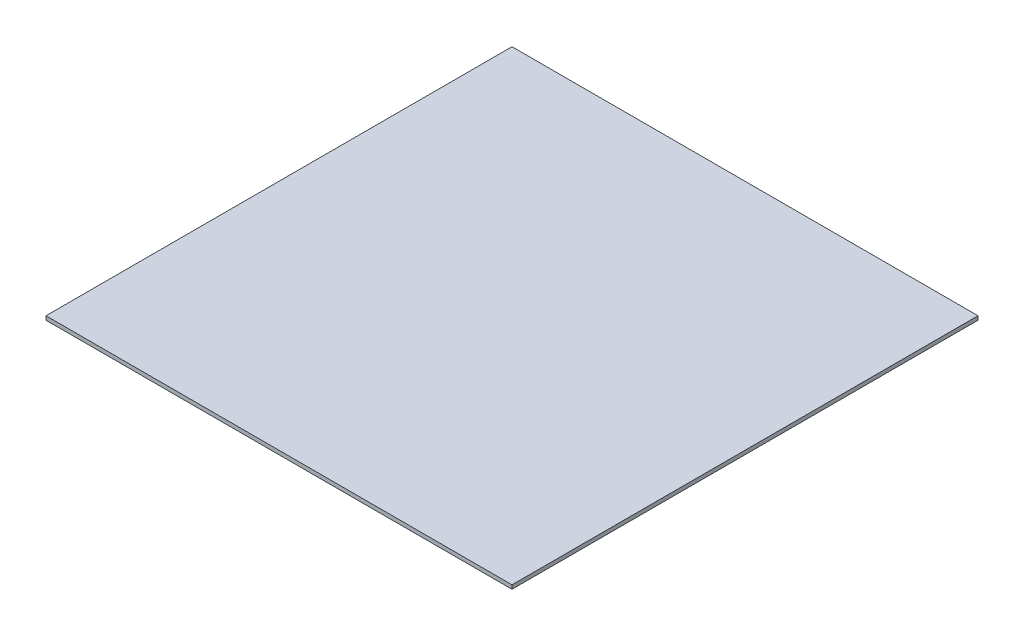
SolidWorks part; units mm, degrees
ref_plane "Front Plane" through (0, 0, 0) normal (0, 0, 1) x (1, 0, 0)
ref_plane "Top Plane" through (0, 0, 0) normal (0, 1, 0) x (1, 0, 0)
ref_plane "Right Plane" through (0, 0, 0) normal (1, 0, 0) x (0, 0, -1)
sketch "Sketch1" plane through (-19.0745, -1092.5733, -406.9173) normal (0, -1, 0) x (1, 0, 0)
  line L5 (-240, -240) -> (240, -240) construction
  line L6 (-240, -240) -> (-240, 240) construction
  line L7 (-240, 240) -> (240, 240) construction
  line L8 (240, -240) -> (240, 240) construction
  line L9 (-240, -240) -> (240, 240) construction
  line L10 (-240, 240) -> (240, -240) construction
  line L11 (300, -300) -> (-300, -300)
  line L12 (300, -300) -> (300, 300)
  line L13 (300, 300) -> (-300, 300)
  line L14 (-300, -300) -> (-300, 300)
  line L15 (300, -300) -> (-300, 300) construction
  line L16 (300, 300) -> (-300, -300) construction
  point P0 (0, 0)
  point P5 (0, 0)
  point P7 (-240, -240)
  dimension "D1" = 480
  dimension "D2" = 480
  dimension "D3" = 600
  dimension "D4" = 600
extrude "Boss-Extrude1" add sketch "Sketch1" along normal blind 5 contours L13 L14 L11 L12
sketch "Sketch3" plane through (0, -1092.5733, 0) normal (0, 1, 0) x (1, 0, 0)
  line L0 (-199.0745, 166.9173) -> (-199.0745, 226.9173)
  line L1 (-259.0745, 166.9173) -> (-199.0745, 166.9173)
  line L2 (-259.0745, 166.9173) -> (-259.0745, 226.9173)
  line L3 (-259.0745, 226.9173) -> (-199.0745, 226.9173)
  line L4 (-199.0745, 166.9173) -> (-199.0745, 226.9173)
  line L5 (-199.0745, 166.9173) -> (-139.0745, 166.9173)
  line L6 (-139.0745, 166.9173) -> (-139.0745, 226.9173)
  line L7 (-199.0745, 226.9173) -> (-139.0745, 226.9173)
  line L8 (-139.0745, 166.9173) -> (-139.0745, 226.9173)
  line L9 (-139.0745, 166.9173) -> (-79.0745, 166.9173)
  line L10 (-79.0745, 166.9173) -> (-79.0745, 226.9173)
  line L11 (-139.0745, 226.9173) -> (-79.0745, 226.9173)
  line L12 (-79.0745, 166.9173) -> (-79.0745, 226.9173)
  line L13 (-79.0745, 166.9173) -> (-19.0745, 166.9173)
  line L14 (-19.0745, 166.9173) -> (-19.0745, 226.9173)
  line L15 (-79.0745, 226.9173) -> (-19.0745, 226.9173)
  line L16 (-19.0745, 166.9173) -> (-19.0745, 226.9173)
  line L17 (-19.0745, 166.9173) -> (40.9255, 166.9173)
  line L18 (40.9255, 166.9173) -> (40.9255, 226.9173)
  line L19 (-19.0745, 226.9173) -> (40.9255, 226.9173)
  line L20 (40.9255, 166.9173) -> (40.9255, 226.9173)
  line L21 (40.9255, 166.9173) -> (100.9255, 166.9173)
  line L22 (100.9255, 166.9173) -> (100.9255, 226.9173)
  line L23 (40.9255, 226.9173) -> (100.9255, 226.9173)
  line L24 (100.9255, 166.9173) -> (100.9255, 226.9173)
  line L25 (100.9255, 166.9173) -> (160.9255, 166.9173)
  line L26 (160.9255, 166.9173) -> (160.9255, 226.9173)
  line L27 (100.9255, 226.9173) -> (160.9255, 226.9173)
  line L28 (160.9255, 166.9173) -> (160.9255, 226.9173)
  line L29 (160.9255, 166.9173) -> (220.9255, 166.9173)
  line L30 (220.9255, 166.9173) -> (220.9255, 226.9173)
  line L31 (160.9255, 226.9173) -> (220.9255, 226.9173)
  line L32 (-199.0745, 226.9173) -> (-199.0745, 286.9173)
  line L33 (-199.0745, 226.9173) -> (-139.0745, 226.9173)
  line L34 (-139.0745, 226.9173) -> (-139.0745, 286.9173)
  line L35 (-199.0745, 286.9173) -> (-139.0745, 286.9173)
  line L36 (-139.0745, 226.9173) -> (-139.0745, 286.9173)
  line L37 (-139.0745, 226.9173) -> (-79.0745, 226.9173)
  line L38 (-79.0745, 226.9173) -> (-79.0745, 286.9173)
  line L39 (-139.0745, 286.9173) -> (-79.0745, 286.9173)
  line L40 (-79.0745, 226.9173) -> (-79.0745, 286.9173)
  line L41 (-79.0745, 226.9173) -> (-19.0745, 226.9173)
  line L42 (-19.0745, 226.9173) -> (-19.0745, 286.9173)
  line L43 (-79.0745, 286.9173) -> (-19.0745, 286.9173)
  line L44 (-19.0745, 226.9173) -> (-19.0745, 286.9173)
  line L45 (-19.0745, 226.9173) -> (40.9255, 226.9173)
  line L46 (40.9255, 226.9173) -> (40.9255, 286.9173)
  line L47 (-19.0745, 286.9173) -> (40.9255, 286.9173)
  line L48 (40.9255, 226.9173) -> (40.9255, 286.9173)
  line L49 (40.9255, 226.9173) -> (100.9255, 226.9173)
  line L50 (100.9255, 226.9173) -> (100.9255, 286.9173)
  line L51 (40.9255, 286.9173) -> (100.9255, 286.9173)
  line L52 (100.9255, 226.9173) -> (100.9255, 286.9173)
  line L53 (100.9255, 226.9173) -> (160.9255, 226.9173)
  line L54 (160.9255, 226.9173) -> (160.9255, 286.9173)
  line L55 (100.9255, 286.9173) -> (160.9255, 286.9173)
  line L56 (160.9255, 226.9173) -> (160.9255, 286.9173)
  line L57 (160.9255, 226.9173) -> (220.9255, 226.9173)
  line L58 (220.9255, 226.9173) -> (220.9255, 286.9173)
  line L59 (160.9255, 286.9173) -> (220.9255, 286.9173)
  line L60 (-199.0745, 286.9173) -> (-199.0745, 346.9173)
  line L61 (-199.0745, 286.9173) -> (-139.0745, 286.9173)
  line L62 (-139.0745, 286.9173) -> (-139.0745, 346.9173)
  line L63 (-199.0745, 346.9173) -> (-139.0745, 346.9173)
  line L64 (-139.0745, 286.9173) -> (-139.0745, 346.9173)
  line L65 (-139.0745, 286.9173) -> (-79.0745, 286.9173)
  line L66 (-79.0745, 286.9173) -> (-79.0745, 346.9173)
  line L67 (-139.0745, 346.9173) -> (-79.0745, 346.9173)
  line L68 (-79.0745, 286.9173) -> (-79.0745, 346.9173)
  line L69 (-79.0745, 286.9173) -> (-19.0745, 286.9173)
  line L70 (-19.0745, 286.9173) -> (-19.0745, 346.9173)
  line L71 (-79.0745, 346.9173) -> (-19.0745, 346.9173)
  line L72 (-19.0745, 286.9173) -> (-19.0745, 346.9173)
  line L73 (-19.0745, 286.9173) -> (40.9255, 286.9173)
  line L74 (40.9255, 286.9173) -> (40.9255, 346.9173)
  line L75 (-19.0745, 346.9173) -> (40.9255, 346.9173)
  line L76 (40.9255, 286.9173) -> (40.9255, 346.9173)
  line L77 (40.9255, 286.9173) -> (100.9255, 286.9173)
  line L78 (100.9255, 286.9173) -> (100.9255, 346.9173)
  line L79 (40.9255, 346.9173) -> (100.9255, 346.9173)
  line L80 (100.9255, 286.9173) -> (100.9255, 346.9173)
  line L81 (100.9255, 286.9173) -> (160.9255, 286.9173)
  line L82 (160.9255, 286.9173) -> (160.9255, 346.9173)
  line L83 (100.9255, 346.9173) -> (160.9255, 346.9173)
  line L84 (160.9255, 286.9173) -> (160.9255, 346.9173)
  line L85 (160.9255, 286.9173) -> (220.9255, 286.9173)
  line L86 (220.9255, 286.9173) -> (220.9255, 346.9173)
  line L87 (160.9255, 346.9173) -> (220.9255, 346.9173)
  line L88 (-199.0745, 346.9173) -> (-199.0745, 406.9173)
  line L89 (-199.0745, 346.9173) -> (-139.0745, 346.9173)
  line L90 (-139.0745, 346.9173) -> (-139.0745, 406.9173)
  line L91 (-199.0745, 406.9173) -> (-139.0745, 406.9173)
  line L92 (-139.0745, 346.9173) -> (-139.0745, 406.9173)
  line L93 (-139.0745, 346.9173) -> (-79.0745, 346.9173)
  line L94 (-79.0745, 346.9173) -> (-79.0745, 406.9173)
  line L95 (-139.0745, 406.9173) -> (-79.0745, 406.9173)
  line L96 (-79.0745, 346.9173) -> (-79.0745, 406.9173)
  line L97 (-79.0745, 346.9173) -> (-19.0745, 346.9173)
  line L98 (-19.0745, 346.9173) -> (-19.0745, 406.9173)
  line L99 (-79.0745, 406.9173) -> (-19.0745, 406.9173)
  line L100 (-19.0745, 346.9173) -> (-19.0745, 406.9173)
  line L101 (-19.0745, 346.9173) -> (40.9255, 346.9173)
  line L102 (40.9255, 346.9173) -> (40.9255, 406.9173)
  line L103 (-19.0745, 406.9173) -> (40.9255, 406.9173)
  line L104 (40.9255, 346.9173) -> (40.9255, 406.9173)
  line L105 (40.9255, 346.9173) -> (100.9255, 346.9173)
  line L106 (100.9255, 346.9173) -> (100.9255, 406.9173)
  line L107 (40.9255, 406.9173) -> (100.9255, 406.9173)
  line L108 (100.9255, 346.9173) -> (100.9255, 406.9173)
  line L109 (100.9255, 346.9173) -> (160.9255, 346.9173)
  line L110 (160.9255, 346.9173) -> (160.9255, 406.9173)
  line L111 (100.9255, 406.9173) -> (160.9255, 406.9173)
  line L112 (160.9255, 346.9173) -> (160.9255, 406.9173)
  line L113 (160.9255, 346.9173) -> (220.9255, 346.9173)
  line L114 (220.9255, 346.9173) -> (220.9255, 406.9173)
  line L115 (160.9255, 406.9173) -> (220.9255, 406.9173)
  line L116 (-199.0745, 406.9173) -> (-199.0745, 466.9173)
  line L117 (-199.0745, 406.9173) -> (-139.0745, 406.9173)
  line L118 (-139.0745, 406.9173) -> (-139.0745, 466.9173)
  line L119 (-199.0745, 466.9173) -> (-139.0745, 466.9173)
  line L120 (-139.0745, 406.9173) -> (-139.0745, 466.9173)
  line L121 (-139.0745, 406.9173) -> (-79.0745, 406.9173)
  line L122 (-79.0745, 406.9173) -> (-79.0745, 466.9173)
  line L123 (-139.0745, 466.9173) -> (-79.0745, 466.9173)
  line L124 (-79.0745, 406.9173) -> (-79.0745, 466.9173)
  line L125 (-79.0745, 406.9173) -> (-19.0745, 406.9173)
  line L126 (-19.0745, 406.9173) -> (-19.0745, 466.9173)
  line L127 (-79.0745, 466.9173) -> (-19.0745, 466.9173)
  line L128 (-19.0745, 406.9173) -> (-19.0745, 466.9173)
  line L129 (-19.0745, 406.9173) -> (40.9255, 406.9173)
  line L130 (40.9255, 406.9173) -> (40.9255, 466.9173)
  line L131 (-19.0745, 466.9173) -> (40.9255, 466.9173)
  line L132 (40.9255, 406.9173) -> (40.9255, 466.9173)
  line L133 (40.9255, 406.9173) -> (100.9255, 406.9173)
  line L134 (100.9255, 406.9173) -> (100.9255, 466.9173)
  line L135 (40.9255, 466.9173) -> (100.9255, 466.9173)
  line L136 (100.9255, 406.9173) -> (100.9255, 466.9173)
  line L137 (100.9255, 406.9173) -> (160.9255, 406.9173)
  line L138 (160.9255, 406.9173) -> (160.9255, 466.9173)
  line L139 (100.9255, 466.9173) -> (160.9255, 466.9173)
  line L140 (160.9255, 406.9173) -> (160.9255, 466.9173)
  line L141 (160.9255, 406.9173) -> (220.9255, 406.9173)
  line L142 (220.9255, 406.9173) -> (220.9255, 466.9173)
  line L143 (160.9255, 466.9173) -> (220.9255, 466.9173)
  line L144 (-199.0745, 466.9173) -> (-199.0745, 526.9173)
  line L145 (-199.0745, 466.9173) -> (-139.0745, 466.9173)
  line L146 (-139.0745, 466.9173) -> (-139.0745, 526.9173)
  line L147 (-199.0745, 526.9173) -> (-139.0745, 526.9173)
  line L148 (-139.0745, 466.9173) -> (-139.0745, 526.9173)
  line L149 (-139.0745, 466.9173) -> (-79.0745, 466.9173)
  line L150 (-79.0745, 466.9173) -> (-79.0745, 526.9173)
  line L151 (-139.0745, 526.9173) -> (-79.0745, 526.9173)
  line L152 (-79.0745, 466.9173) -> (-79.0745, 526.9173)
  line L153 (-79.0745, 466.9173) -> (-19.0745, 466.9173)
  line L154 (-19.0745, 466.9173) -> (-19.0745, 526.9173)
  line L155 (-79.0745, 526.9173) -> (-19.0745, 526.9173)
  line L156 (-19.0745, 466.9173) -> (-19.0745, 526.9173)
  line L157 (-19.0745, 466.9173) -> (40.9255, 466.9173)
  line L158 (40.9255, 466.9173) -> (40.9255, 526.9173)
  line L159 (-19.0745, 526.9173) -> (40.9255, 526.9173)
  line L160 (40.9255, 466.9173) -> (40.9255, 526.9173)
  line L161 (40.9255, 466.9173) -> (100.9255, 466.9173)
  line L162 (100.9255, 466.9173) -> (100.9255, 526.9173)
  line L163 (40.9255, 526.9173) -> (100.9255, 526.9173)
  line L164 (100.9255, 466.9173) -> (100.9255, 526.9173)
  line L165 (100.9255, 466.9173) -> (160.9255, 466.9173)
  line L166 (160.9255, 466.9173) -> (160.9255, 526.9173)
  line L167 (100.9255, 526.9173) -> (160.9255, 526.9173)
  line L168 (160.9255, 466.9173) -> (160.9255, 526.9173)
  line L169 (160.9255, 466.9173) -> (220.9255, 466.9173)
  line L170 (220.9255, 466.9173) -> (220.9255, 526.9173)
  line L171 (160.9255, 526.9173) -> (220.9255, 526.9173)
  line L172 (-199.0745, 526.9173) -> (-199.0745, 586.9173)
  line L173 (-199.0745, 526.9173) -> (-139.0745, 526.9173)
  line L174 (-139.0745, 526.9173) -> (-139.0745, 586.9173)
  line L175 (-199.0745, 586.9173) -> (-139.0745, 586.9173)
  line L176 (-139.0745, 526.9173) -> (-139.0745, 586.9173)
  line L177 (-139.0745, 526.9173) -> (-79.0745, 526.9173)
  line L178 (-79.0745, 526.9173) -> (-79.0745, 586.9173)
  line L179 (-139.0745, 586.9173) -> (-79.0745, 586.9173)
  line L180 (-79.0745, 526.9173) -> (-79.0745, 586.9173)
  line L181 (-79.0745, 526.9173) -> (-19.0745, 526.9173)
  line L182 (-19.0745, 526.9173) -> (-19.0745, 586.9173)
  line L183 (-79.0745, 586.9173) -> (-19.0745, 586.9173)
  line L184 (-19.0745, 526.9173) -> (-19.0745, 586.9173)
  line L185 (-19.0745, 526.9173) -> (40.9255, 526.9173)
  line L186 (40.9255, 526.9173) -> (40.9255, 586.9173)
  line L187 (-19.0745, 586.9173) -> (40.9255, 586.9173)
  line L188 (40.9255, 526.9173) -> (40.9255, 586.9173)
  line L189 (40.9255, 526.9173) -> (100.9255, 526.9173)
  line L190 (100.9255, 526.9173) -> (100.9255, 586.9173)
  line L191 (40.9255, 586.9173) -> (100.9255, 586.9173)
  line L192 (100.9255, 526.9173) -> (100.9255, 586.9173)
  line L193 (100.9255, 526.9173) -> (160.9255, 526.9173)
  line L194 (160.9255, 526.9173) -> (160.9255, 586.9173)
  line L195 (100.9255, 586.9173) -> (160.9255, 586.9173)
  line L196 (160.9255, 526.9173) -> (160.9255, 586.9173)
  line L197 (160.9255, 526.9173) -> (220.9255, 526.9173)
  line L198 (220.9255, 526.9173) -> (220.9255, 586.9173)
  line L199 (160.9255, 586.9173) -> (220.9255, 586.9173)
  line L200 (-199.0745, 586.9173) -> (-199.0745, 646.9173)
  line L201 (-199.0745, 586.9173) -> (-139.0745, 586.9173)
  line L202 (-139.0745, 586.9173) -> (-139.0745, 646.9173)
  line L203 (-199.0745, 646.9173) -> (-139.0745, 646.9173)
  line L204 (-139.0745, 586.9173) -> (-139.0745, 646.9173)
  line L205 (-139.0745, 586.9173) -> (-79.0745, 586.9173)
  line L206 (-79.0745, 586.9173) -> (-79.0745, 646.9173)
  line L207 (-139.0745, 646.9173) -> (-79.0745, 646.9173)
  line L208 (-79.0745, 586.9173) -> (-79.0745, 646.9173)
  line L209 (-79.0745, 586.9173) -> (-19.0745, 586.9173)
  line L210 (-19.0745, 586.9173) -> (-19.0745, 646.9173)
  line L211 (-79.0745, 646.9173) -> (-19.0745, 646.9173)
  line L212 (-19.0745, 586.9173) -> (-19.0745, 646.9173)
  line L213 (-19.0745, 586.9173) -> (40.9255, 586.9173)
  line L214 (40.9255, 586.9173) -> (40.9255, 646.9173)
  line L215 (-19.0745, 646.9173) -> (40.9255, 646.9173)
  line L216 (40.9255, 586.9173) -> (40.9255, 646.9173)
  line L217 (40.9255, 586.9173) -> (100.9255, 586.9173)
  line L218 (100.9255, 586.9173) -> (100.9255, 646.9173)
  line L219 (40.9255, 646.9173) -> (100.9255, 646.9173)
  line L220 (100.9255, 586.9173) -> (100.9255, 646.9173)
  line L221 (100.9255, 586.9173) -> (160.9255, 586.9173)
  line L222 (160.9255, 586.9173) -> (160.9255, 646.9173)
  line L223 (100.9255, 646.9173) -> (160.9255, 646.9173)
  line L224 (160.9255, 586.9173) -> (160.9255, 646.9173)
  line L225 (160.9255, 586.9173) -> (220.9255, 586.9173)
  line L226 (220.9255, 586.9173) -> (220.9255, 646.9173)
  line L227 (160.9255, 646.9173) -> (220.9255, 646.9173)
  line L228 (-259.0745, 226.9173) -> (-259.0745, 286.9173)
  line L229 (-259.0745, 226.9173) -> (-199.0745, 226.9173)
  line L230 (-199.0745, 226.9173) -> (-199.0745, 286.9173)
  line L231 (-259.0745, 286.9173) -> (-199.0745, 286.9173)
  line L232 (-259.0745, 286.9173) -> (-259.0745, 346.9173)
  line L233 (-259.0745, 286.9173) -> (-199.0745, 286.9173)
  line L234 (-199.0745, 286.9173) -> (-199.0745, 346.9173)
  line L235 (-259.0745, 346.9173) -> (-199.0745, 346.9173)
  line L236 (-259.0745, 346.9173) -> (-259.0745, 406.9173)
  line L237 (-259.0745, 346.9173) -> (-199.0745, 346.9173)
  line L238 (-199.0745, 346.9173) -> (-199.0745, 406.9173)
  line L239 (-259.0745, 406.9173) -> (-199.0745, 406.9173)
  line L240 (-259.0745, 406.9173) -> (-259.0745, 466.9173)
  line L241 (-259.0745, 406.9173) -> (-199.0745, 406.9173)
  line L242 (-199.0745, 406.9173) -> (-199.0745, 466.9173)
  line L243 (-259.0745, 466.9173) -> (-199.0745, 466.9173)
  line L244 (-259.0745, 466.9173) -> (-259.0745, 526.9173)
  line L245 (-259.0745, 466.9173) -> (-199.0745, 466.9173)
  line L246 (-199.0745, 466.9173) -> (-199.0745, 526.9173)
  line L247 (-259.0745, 526.9173) -> (-199.0745, 526.9173)
  line L248 (-259.0745, 526.9173) -> (-259.0745, 586.9173)
  line L249 (-259.0745, 526.9173) -> (-199.0745, 526.9173)
  line L250 (-199.0745, 526.9173) -> (-199.0745, 586.9173)
  line L251 (-259.0745, 586.9173) -> (-199.0745, 586.9173)
  line L252 (-259.0745, 586.9173) -> (-259.0745, 646.9173)
  line L253 (-259.0745, 586.9173) -> (-199.0745, 586.9173)
  line L254 (-199.0745, 586.9173) -> (-199.0745, 646.9173)
  line L255 (-259.0745, 646.9173) -> (-199.0745, 646.9173)
  point P5 (0, 0)
  dimension "D1" = 60
  dimension "D2" = 60
  dimension "D3" = 8
  dimension "D4" = 8
